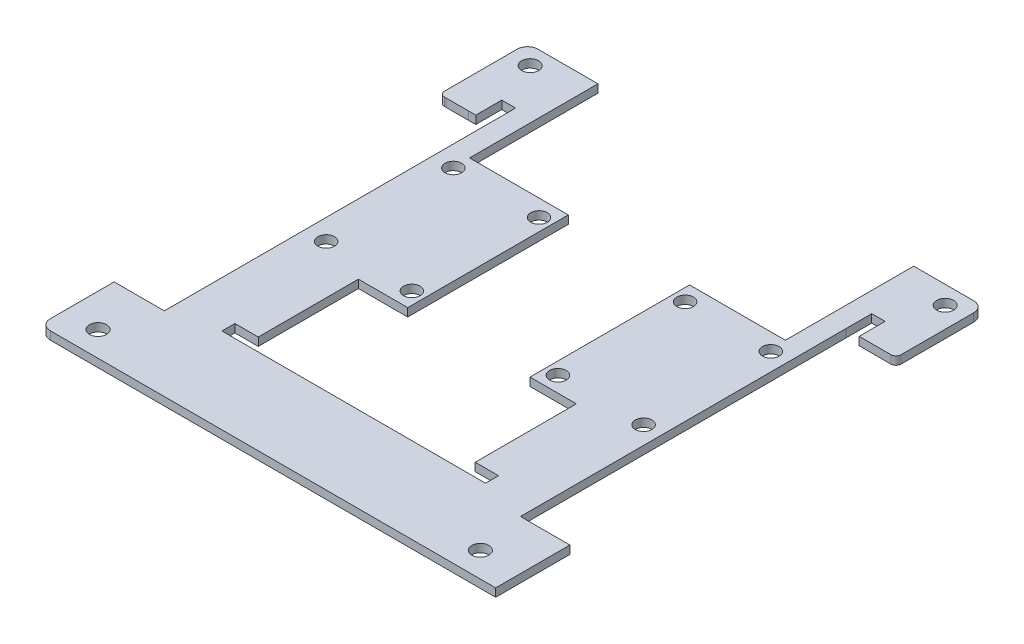
SolidWorks part; units mm, degrees
material "Copper"
ref_plane "Front Plane" through (0, 0, 0) normal (0, 0, 1) x (1, 0, 0)
ref_plane "Top Plane" through (0, 0, 0) normal (0, 1, 0) x (1, 0, 0)
ref_plane "Right Plane" through (0, 0, 0) normal (1, 0, 0) x (0, 0, -1)
sketch "Sketch1" plane through (0, 0, 0) normal (0, 1, 0) x (1, 0, 0)
  line L0 (-38.395, 30) -> (-42.73, 30)
  line L1 (-44, 31.27) -> (-44, 45)
  line L2 (42, 47) -> (30.435, 47)
  line L3 (44, 45) -> (44, 32)
  line L4 (44, 32) -> (44, 31.0156)
  line L5 (42.9984, 30.0156) -> (33.8256, 30.0304)
  line L6 (32.824, 29.0304) -> (32.824, -30.454)
  line L7 (-44, -38.977) -> (-44, -32.454)
  line L8 (-42, -47) -> (43.8497, -47)
  line L9 (-44, -45) -> (-44, -38.977)
  line L10 (-43, -31.454) -> (-36.1, -31.454)
  line L11 (43.8497, -37) -> (43.8497, -32.454)
  line L12 (42.8497, -31.454) -> (36.1, -31.454)
  line L13 (23.409, -31.5) -> (-23.409, -31.5)
  line L14 (-11.409, -9.9) -> (-23.409, -9.9)
  line L15 (30.435, 22.2554) -> (11.9708, 22.2554)
  line L16 (-11.409, -9.9) -> (-11.409, 22.2554)
  line L17 (30.435, 47) -> (30.435, 22.2554)
  line L18 (11.9708, 22.2554) -> (11.9708, -8.5)
  line L19 (-23.409, -31.5) -> (-23.409, -9.9)
  line L20 (11.9708, -8.5) -> (23.409, -8.5)
  line L21 (-36.1, -31.454) -> (-33.824, -31.454)
  line L22 (-32.824, -30.454) -> (-32.824, 29.0115)
  line L23 (-33.8265, 30.0115) -> (-38.395, 30)
  line L24 (-42.73, 30) -> (-43.011, 30.0031)
  line L25 (-44, 31.003) -> (-44, 31.27)
  line L28 (43.8497, -47) -> (43.8497, -37)
  line L33 (33.824, -31.454) -> (36.1, -31.454)
  line L34 (-23.409, 13.2954) -> (-23.409, -31.5) construction
  line L35 (23.409, -31.5) -> (23.409, -8.5)
  line L41 (-42, 47) -> (-30.435, 47)
  line L42 (-30.435, 47) -> (-30.435, 22.2554)
  line L43 (-30.435, 22.2554) -> (-11.409, 22.2554)
  circle A0 centre (40, 43.5) radius 1.6383
  circle A1 centre (-40, 43.5) radius 1.6383
  circle A2 centre (-37.6, -42.2) radius 1.6383
  circle A3 centre (36.1, -42.2) radius 1.6383
  arc A5 (-42, 47) -> (-44, 45) centre (-42, 45) ccw
  arc A6 (44, 45) -> (42, 47) centre (42, 45) ccw
  arc A9 (-43.011, 30.0031) -> (-44, 31.003) centre (-43, 31.003) cw
  arc A10 (-32.824, 29.0115) -> (-33.8265, 30.0115) centre (-33.824, 29.0115) ccw
  arc A11 (-44, -45) -> (-42, -47) centre (-42, -45) ccw
  arc A12 (44, 31.0156) -> (42.9984, 30.0156) centre (43, 31.0156) cw
  arc A14 (33.8256, 30.0304) -> (32.824, 29.0304) centre (33.824, 29.0304) ccw
  arc A15 (43.8497, -32.454) -> (42.8497, -31.454) centre (42.8497, -32.454) ccw
  arc A16 (32.824, -30.454) -> (33.824, -31.454) centre (33.824, -30.454) ccw
  arc A17 (-33.824, -31.454) -> (-32.824, -30.454) centre (-33.824, -30.454) ccw
  arc A18 (-44, -32.454) -> (-43, -31.454) centre (-43, -32.454) cw
  point P37 (-44, 30.014)
  point P48 (-32.824, 30.014)
  point P61 (44, 30.014)
  point P80 (32.824, 30.032)
  point P95 (32.824, -31.454)
  point P98 (-32.824, -31.454)
  dimension "D1" = 1
  dimension "D2" = 73.7
  dimension "D3" = 85.7
  dimension "D4" = 80
  dimension "D5" = 85.7
  dimension "D6" = 19.026
  dimension "D7" = 12
  dimension "D8" = 18.4641
  dimension "D9" = 11.4381
  dimension "D10" = 32.1554
  dimension "D11" = 21.6
extrude "Boss-Extrude1" [suppressed] add sketch "Sketch1" along normal blind 1.575
extrude "Boss-Extrude2" add sketch "Sketch1<2>" along normal blind 1.575
sketch "Sketch1<2>" plane through (0, 0, 0) normal (0, 1, 0) x (1, 0, 0) same geometry as "Sketch1"
sketch "Sketch2" plane through (0, 1.575, 0) normal (0, 1, 0) x (1, 0, 0)
  line L1 (32.8227, -32.694) -> (46.9034, -32.694)
  line L2 (32.8227, -32.694) -> (32.8227, -25.5777)
  line L3 (32.8227, -25.5777) -> (46.9034, -25.5777)
  line L4 (46.9034, -32.694) -> (46.9034, -25.5777)
  line L5 (-47.8402, -23.2727) -> (-32.833, -23.2727)
  line L6 (-47.8402, -23.2727) -> (-47.8402, -32.694)
  line L7 (-47.8402, -32.694) -> (-32.833, -32.694)
  line L8 (-32.833, -23.2727) -> (-32.833, -32.694)
  dimension "D1" = 14.306
  dimension "D2" = 11.027
  dimension "D3" = 11.167
  dimension "D4" = 14.306
extrude "Cut-Extrude1" cut sketch "Sketch2" against normal through all
sketch "Additional PCB material" plane through (0, 1.575, 0) normal (0, 1, 0) x (1, 0, 0)
  line L0 (32.824, 29.0304) -> (32.824, -30.454) construction
  line L1 (31.6745, 31.4781) -> (34.324, 31.4781)
  line L2 (31.6745, 31.4781) -> (31.6745, -33.7352)
  line L3 (31.6745, -33.7352) -> (34.324, -33.7352)
  line L4 (34.324, 31.4781) -> (34.324, -33.7352)
  line L5 (-34.324, 31.564) -> (-32.824, 31.564)
  line L6 (-34.324, 31.564) -> (-34.324, -33.7352)
  line L7 (-34.324, -33.7352) -> (-32.824, -33.7352)
  line L8 (-32.824, 31.564) -> (-32.824, -33.7352)
  dimension "D1" = 1.5
  dimension "D2" = 1.5
  dimension "D3" = 1.5
extrude "Boss-Extrude3" add sketch "Additional PCB material" against normal blind 1.575
sketch "Sketch3" plane through (0, 1.575, 0) normal (0, 1, 0) x (1, 0, 0)
  line L0 (23.409, -31.5) -> (23.409, -8.5) construction
  line L1 (-23.409, -31.5) -> (23.409, -31.5)
  line L2 (-23.409, -31.5) -> (-23.409, -30.5)
  line L3 (-23.409, -30.5) -> (23.409, -30.5)
  line L4 (23.409, -31.5) -> (23.409, -30.5)
  dimension "D1" = 1
extrude "Boss-Extrude4" add sketch "Sketch3" against normal blind 1.575
sketch "Sketch4" plane through (0, 1.575, 0) normal (0, 1, 0) x (1, 0, 0)
  line L1 (23.409, -30.5) -> (25.409, -30.5)
  line L2 (23.409, -30.5) -> (23.409, -28)
  line L3 (23.409, -28) -> (25.409, -28)
  line L4 (25.409, -30.5) -> (25.409, -28)
  line L5 (-23.409, -30.5) -> (-25.409, -30.5)
  line L6 (-23.409, -30.5) -> (-23.409, -28)
  line L7 (-23.409, -28) -> (-25.409, -28)
  line L8 (-25.409, -30.5) -> (-25.409, -28)
  dimension "D1" = 2.5
  dimension "D2" = 2
  dimension "D3" = 2.5
  dimension "D4" = 2
extrude "Cut-Extrude2" cut sketch "Sketch4" against normal through all
sketch "Sketch5" plane through (0, 1.575, 0) normal (0, 1, 0) x (1, 0, 0)
  line L0 (-11.409, -9.9) -> (-23.409, -9.9) construction
  line L1 (-23.409, -28) -> (-20.909, -28)
  line L2 (-23.409, -28) -> (-23.409, -9.9)
  line L3 (-23.409, -9.9) -> (-20.909, -9.9)
  line L4 (-20.909, -28) -> (-20.909, -9.9)
  line L5 (11.9708, -8.5) -> (23.409, -8.5) construction
  line L6 (23.409, -28) -> (20.909, -28)
  line L7 (23.409, -28) -> (23.409, -8.5)
  line L8 (23.409, -8.5) -> (20.909, -8.5)
  line L9 (20.909, -28) -> (20.909, -8.5)
  dimension "D1" = 2.5
  dimension "D2" = 2.5
extrude "Boss-Extrude5" add sketch "Sketch5" against normal blind 1.575
sketch "Sketch7" plane through (0, 1.575, 0) normal (0, 1, 0) x (1, 0, 0)
  line L1 (-11.409, -9.9) -> (-20.909, -9.9)
  line L2 (-11.409, -9.9) -> (-11.409, -8.694)
  line L3 (-11.409, -8.694) -> (-20.909, -8.694)
  line L4 (-20.909, -9.9) -> (-20.909, -8.694)
  dimension "D1" = 24
extrude "Cut-Extrude3" cut sketch "Sketch7" against normal through all
hole_wizard "M3 Clearance Hole1" positions "Sketch8" profile "Sketch9" hole size "M3" standard "ISO" end condition through all
sketch "Sketch8" plane through (-37.3577, 1.575, 48.2358) normal (0, 1, 0) x (-1, 0, 0)
  point P0 (-23.5587, -42.7243)
  point P1 (-23.5587, -67.2443)
  point P2 (-7.0387, -67.2443)
  point P3 (-7.0387, -42.7243)
sketch "Sketch9" plane through (-13.799, 1.575, 5.5115) normal (1, 0, 0) x (0, 0, 1)
  line L0 (0, 0) -> (0, 1.575)
  line L1 (0, 1.575) -> (1.6, 1.575)
  line L2 (1.6, 1.575) -> (1.6, 0)
  line L3 (1.6, 0) -> (0, 0)
  line L4 (0, -6.35) -> (0, 107.95) construction
  dimension "Thru Hole Dia." = 3.2
  dimension "Thru Hole Depth" = 1.575
hole_wizard "M3 Clearance Hole2" positions "Sketch18" profile "Sketch19" hole size "M3" standard "ISO" end condition through all
sketch "Sketch18" plane through (-37.3577, 1.575, 48.2358) normal (0, 1, 0) x (-1, 0, 0)
  point P0 (-51.7186, -42.7243)
sketch "Sketch19" plane through (14.3608, 1.575, 5.5115) normal (1, 0, 0) x (0, 0, 1)
  line L0 (0, 0) -> (0, 1.575)
  line L1 (0, 1.575) -> (1.6, 1.575)
  line L2 (1.6, 1.575) -> (1.6, 0)
  line L3 (1.6, 0) -> (0, 0)
  line L4 (0, -6.35) -> (0, 107.95) construction
  dimension "Thru Hole Dia." = 3.2
  dimension "Thru Hole Depth" = 1.575
hole_wizard "M3 Clearance Hole3" positions "Sketch20" profile "Sketch21" hole size "M3" standard "ISO" end condition through all
sketch "Sketch20" plane through (-37.3577, 1.575, 48.2358) normal (0, 1, 0) x (-1, 0, 0)
  point P2 (-68.2386, -42.7243)
sketch "Sketch21" plane through (30.8808, 1.575, 5.5115) normal (1, 0, 0) x (0, 0, 1)
  line L0 (0, 0) -> (0, 1.575)
  line L1 (0, 1.575) -> (1.6, 1.575)
  line L2 (1.6, 1.575) -> (1.6, 0)
  line L3 (1.6, 0) -> (0, 0)
  line L4 (0, -6.35) -> (0, 107.95) construction
  dimension "Thru Hole Dia." = 3.2
  dimension "Thru Hole Depth" = 1.575
hole_wizard "M3 Clearance Hole4" positions "Sketch22" profile "Sketch23" hole size "M3" standard "ISO" end condition through all
sketch "Sketch22" plane through (-37.3577, 21.15, 48.2358) normal (0, 1, 0) x (-1, 0, 0)
  point P0 (-51.7186, -67.2443)
sketch "Sketch23" plane through (14.3608, 21.15, -19.0085) normal (1, 0, 0) x (0, 0, 1)
  line L0 (0, 0) -> (0, 21.15)
  line L1 (0, 21.15) -> (1.6, 21.15)
  line L2 (1.6, 21.15) -> (1.6, 0)
  line L3 (1.6, 0) -> (0, 0)
  line L4 (0, -6.35) -> (0, 107.95) construction
  dimension "Thru Hole Dia." = 3.2
  dimension "Thru Hole Depth" = 21.15
hole_wizard "M3 Clearance Hole5" positions "Sketch24" profile "Sketch25" hole size "M3" standard "ISO" end condition through all
sketch "Sketch24" plane through (-37.3577, 1.575, 48.2358) normal (0, 1, 0) x (-1, 0, 0)
  point P0 (-68.2386, -67.2443)
sketch "Sketch25" plane through (30.8808, 1.575, -19.0085) normal (1, 0, 0) x (0, 0, 1)
  line L0 (0, 0) -> (0, 1.575)
  line L1 (0, 1.575) -> (1.6, 1.575)
  line L2 (1.6, 1.575) -> (1.6, 0)
  line L3 (1.6, 0) -> (0, 0)
  line L4 (0, -6.35) -> (0, 107.95) construction
  dimension "Thru Hole Dia." = 3.2
  dimension "Thru Hole Depth" = 1.575
sketch "Sketch26" plane through (0, 1.575, 0) normal (0, 1, 0) x (1, 0, 0)
  line L0 (44, 45) -> (44, 32) construction
  line L1 (-36.984, 35.0102) -> (-34.324, 35.0102)
  line L2 (-36.984, 35.0102) -> (-36.984, 30.0102)
  line L3 (-34.324, 29.9278) -> (-36.984, 29.9278)
  line L4 (-34.324, 30.0102) -> (-34.324, -32.694) construction
  line L5 (34.325, 35.0156) -> (36.9, 35.0156)
  line L6 (34.325, 35.0156) -> (34.325, 30.0156)
  line L7 (34.325, 30.0156) -> (36.9, 30.0156)
  line L8 (36.9, 35.0156) -> (36.9, 30.0156)
  line L9 (-34.324, 35.0102) -> (-34.324, 29.9278)
  line L10 (-36.984, 30.0102) -> (-36.984, 29.9278)
  dimension "D1" = 7.016
  dimension "D3" = 7.1
  dimension "D4" = 5
  dimension "D5" = 2.575
  dimension "D6" = 5
  dimension "D7" = 5
  dimension "D8" = 0
extrude "Cut-Extrude4" cut sketch "Sketch26" against normal blind 10
